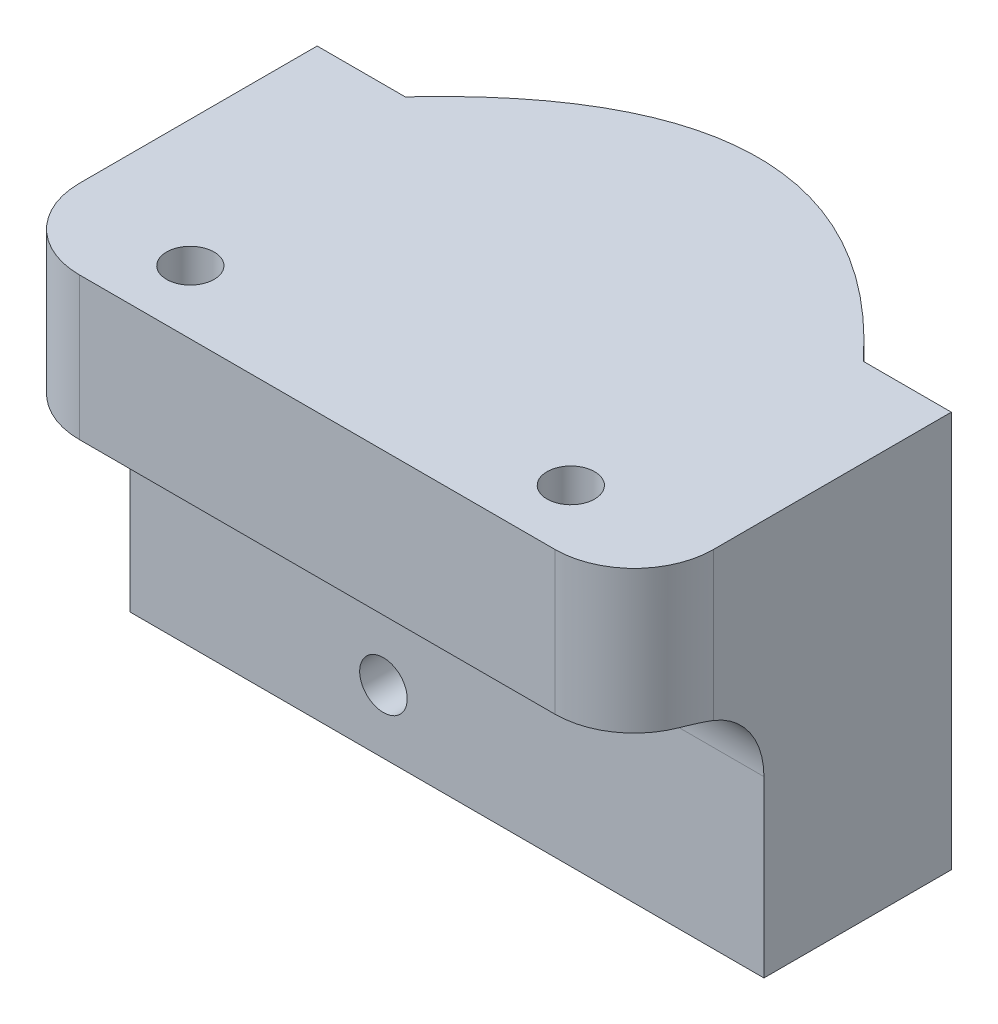
SolidWorks part; units mm, degrees
ref_plane "Front Plane" through (0, 0, 0) normal (0, 0, 1) x (1, 0, 0)
ref_plane "Top Plane" through (0, 0, 0) normal (0, 1, 0) x (1, 0, 0)
ref_plane "Right Plane" through (0, 0, 0) normal (1, 0, 0) x (0, 0, -1)
sketch "Sketch1" plane through (0, 0, 0) normal (0, 1, 0) x (1, 0, 0)
  line L0 (28.89, 0) -> (34.445, 0)
  line L1 (0, 0) -> (28.89, 0)
  line L2 (0, 0) -> (0, 7.82)
  line L3 (0, 7.82) -> (28.89, 7.82)
  line L4 (28.89, 0) -> (28.89, 7.82)
  line L5 (0, 0) -> (-5.555, 0)
  line L6 (-5.555, 0) -> (-5.555, -11.82)
  line L7 (-5.555, -11.82) -> (34.445, -11.82)
  line L8 (34.445, -11.82) -> (34.445, 0)
  line L9 (34.445, -26.82) -> (34.445, 0) construction
  spline S0 degree 2 poles (0, 0) (14.445, 15.64) (28.89, 0) knots 0 0 0 1 1 1
  dimension "D1" = 7.82
  dimension "D2" = 28.89
  dimension "D3" = 11.82
extrude "Boss-Extrude1" add sketch "Sketch1" along normal blind 25 contours S0 L1 | L7 L8 L0 L1 L5 L6 region at (14.445, 0, 5.91) region at (14.445, 0, -3.128)
sketch "Sketch2" plane through (0, 0, 11.82) normal (0, 0, 1) x (1, 0, 0)
  line L0 (34.445, 25) -> (34.445, 0) construction
  line L1 (-5.555, 25) -> (34.445, 25)
  line L2 (-5.555, 25) -> (-5.555, 16)
  line L3 (-5.555, 16) -> (34.445, 16)
  line L4 (34.445, 25) -> (34.445, 16)
extrude "Boss-Extrude2" add sketch "Sketch2" along normal blind 8.18
sketch "Sketch3" plane through (0, 0, 11.82) normal (0, 0, 1) x (1, 0, 0)
  line L0 (14.445, 0) -> (14.445, 16)
  line L3 (-5.555, 0) -> (34.445, 0) construction
  line L4 (-5.555, 16) -> (34.445, 16) construction
  line L5 (14.445, 16) -> (18.445, 16)
  line L6 (18.445, 16) -> (18.445, 12)
  line L7 (14.445, 0) -> (10.445, 0)
  line L8 (10.445, 0) -> (10.445, 4)
  circle A0 centre (18.445, 12) radius 1.5
  circle A1 centre (10.445, 4) radius 1.5
  circle A2 centre (18.445, 12) radius 4
  circle A3 centre (10.445, 4) radius 4
  dimension "D1" = 3
  dimension "D2" = 8
  dimension "D3" = 4
  dimension "D4" = 4
fillet "Fillet1" radius 5 1 edges at (14.445, 16, 11.82)
extrude "Cut-Extrude1" cut sketch "Sketch3" against normal through all both and the other way through all contours A1 | A0 region at (19.4757, 13.0307, 11.82) region at (9.4143, 5.0307, 11.82)
extrude "Cut-Extrude6" cut sketch "Sketch3<4>" along normal through all contours A3 A1 | A2 A0 region at (15.6966, 14.7484, 11.82) region at (13.1934, 1.2516, 11.82)
sketch "Sketch3<4>" plane through (0, 0, 11.82) normal (0, 0, 1) x (1, 0, 0) same geometry as "Sketch3"
sketch "Sketch6" plane through (0, 25, 0) normal (0, 1, 0) x (1, 0, 0)
  line L0 (14.445, -20) -> (14.445, -16)
  line L1 (34.445, -20) -> (-5.555, -20) construction
  line L2 (14.445, -16) -> (26.445, -16)
  line L3 (14.445, -16) -> (2.445, -16)
  circle A0 centre (2.445, -16) radius 1.5
  circle A1 centre (2.445, -16) radius 4
  circle A2 centre (26.445, -16) radius 1.5
  circle A3 centre (26.445, -16) radius 4
  dimension "D1" = 3
  dimension "D2" = 8
  dimension "D3" = 12
  dimension "D4" = 4
extrude "Cut-Extrude7" cut sketch "Sketch6" against normal through all contours A0 | A2 region at (26.445, 25, 14.5424) region at (0.9874, 25, 16)
extrude "Cut-Extrude8" cut sketch "Sketch6<3>" against normal blind 40 from surface contours A1 A0 | A3 A2 region at (26.445, 25, 12.1131) region at (-1.4419, 25, 16) starting at face at (14.8894, 16, 17.6778)
sketch "Sketch6<3>" plane through (0, 25, 0) normal (0, 1, 0) x (1, 0, 0) same geometry as "Sketch6"
fillet "Fillet2" radius 5 2 edges at (34.445, 20.5, 20) (-5.555, 20.5, 20)
